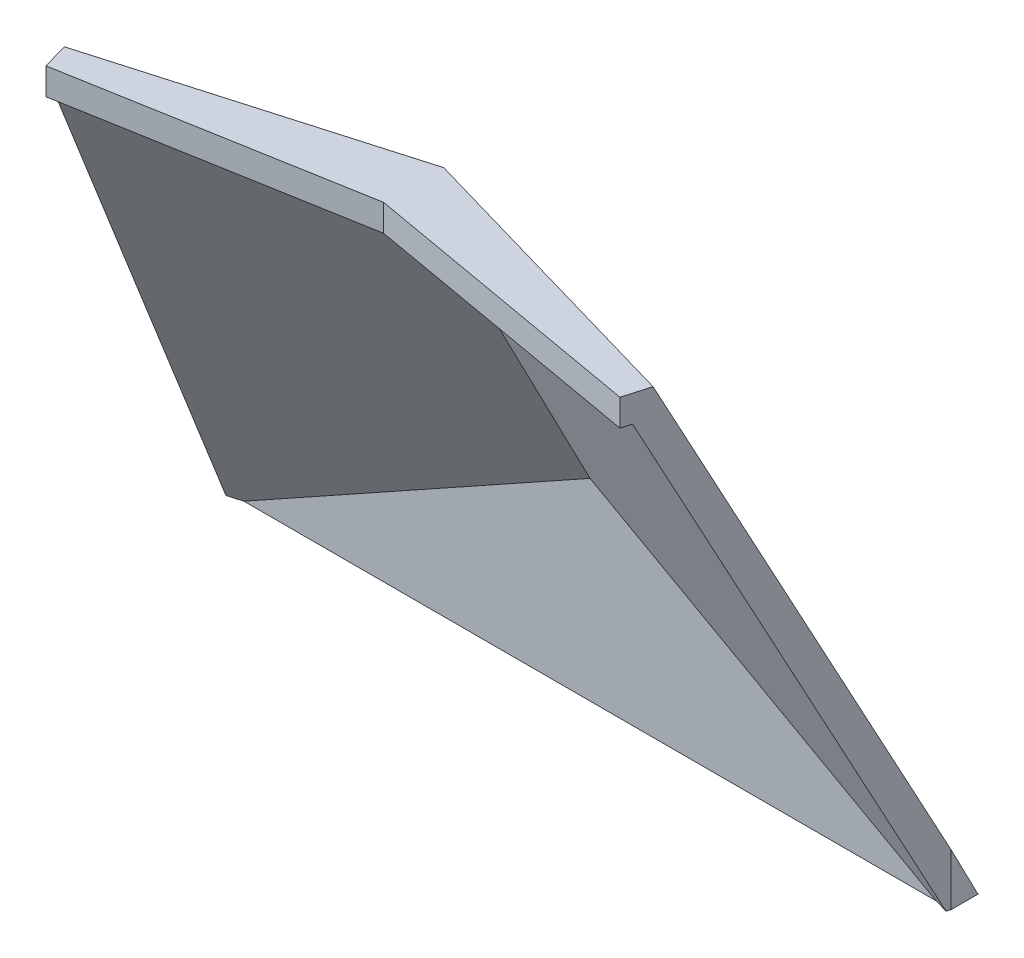
SolidWorks part; units mm, degrees
ref_plane "Front Plane" through (0, 0, 0) normal (0, 0, 1) x (1, 0, 0)
ref_plane "Top Plane" through (0, 0, 0) normal (0, 1, 0) x (1, 0, 0)
ref_plane "Right Plane" through (0, 0, 0) normal (1, 0, 0) x (0, 0, -1)
sketch "Sketch1" plane through (0, 0, 0) normal (0, 1, 0) x (1, 0, 0)
  line L5 (-27, 0) -> (27, 0)
  line L8 (27, 0) -> (27, -2)
  line L9 (-27, 0) -> (-27, -2)
  line L10 (27, -2) -> (21.4507, -21.2147)
  line L11 (-27, -2) -> (-21.4507, -21.2147)
  line L14 (-21.4507, -21.2147) -> (0, -17.4324)
  line L15 (0, -17.4324) -> (21.4507, -21.2147)
  point P16 (0, 0)
  dimension "D7" = 54
  dimension "D8" = 160
  dimension "D9" = 2
  dimension "D10" = 21.7816
  dimension "D11" = 20
  dimension "D12" = 73.891
extrude "Boss-Extrude1" add sketch "Sketch1" along normal blind 40
sketch "Sketch22" plane through (25.4545, 0, 7.3514) normal (0.9607, 0, 0.2775) x (0.2775, 0, -0.9607)
  line L0 (7.4916, 0) -> (-12.4299, 40)
  line L1 (-14.4299, 40) -> (5.5701, 40) construction
  line L2 (-12.4299, 40) -> (7.4916, 40)
  line L3 (7.4916, 40) -> (7.4916, 0)
  line L4 (-14.4299, 40) -> (-14.4299, 0) construction
  dimension "D1" = 2
extrude "Cut-Extrude11" cut sketch "Sketch22" against normal up to vertex (52.4347 mm away) up to point (-27, 40, 0)
sketch "Sketch23" plane through (-25.4545, 0, 7.3514) normal (-0.9607, 0, 0.2775) x (0.2775, 0, 0.9607)
  line L0 (-7.4916, 0) -> (12.4299, 40)
  line L1 (-2.0041, 40) -> (14.4299, 40) construction
  line L2 (12.4299, 40) -> (-7.4916, 40)
  line L3 (-7.4916, 40) -> (-7.4916, 0)
  dimension "D1" = 2
extrude "Cut-Extrude12" cut sketch "Sketch23" against normal up to vertex (52.4347 mm away) up to point (27, 0, 0)
shell "Shell2" thickness 2 removed face at (-27, 1.286, 1.3333) removed face at (-23.7814, 16.7716, 13.1445) removed face at (-10.7253, 20, 19.3235) removed face at (10.7253, 20, 19.3235) removed face at (27, 1.286, 1.3333) removed face at (23.7814, 16.7716, 13.1445) removed face at (0, 0, 9.1231)
